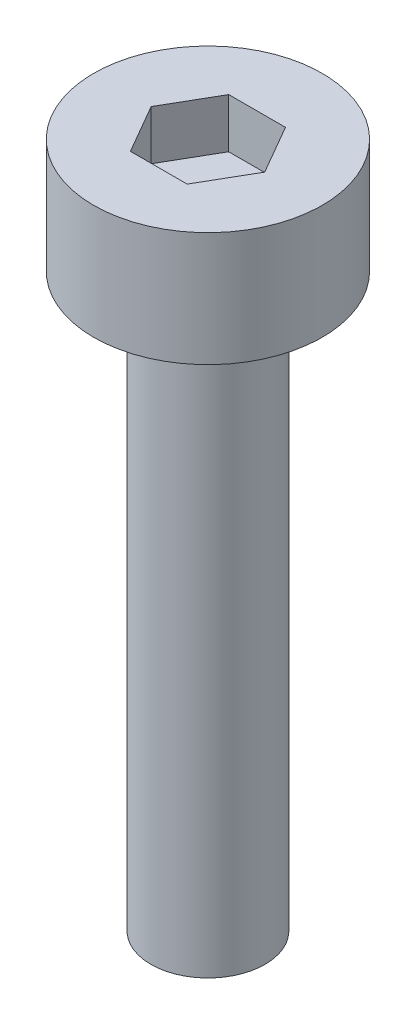
SolidWorks part; units mm, degrees
ref_plane "Front Plane" through (0, 0, 0) normal (0, 0, 1) x (1, 0, 0)
ref_plane "Top Plane" through (0, 0, 0) normal (0, 1, 0) x (1, 0, 0)
ref_plane "Right Plane" through (0, 0, 0) normal (1, 0, 0) x (0, 0, -1)
sketch "Sketch1" plane through (0, 0, 0) normal (0, 1, 0) x (1, 0, 0)
  circle A0 centre (0, 0) radius 1.5
  dimension "D1" = 3
extrude "ScrewShaft" add sketch "Sketch1" along normal blind 15
sketch "Sketch2" plane through (0, 15, 0) normal (0, 1, 0) x (1, 0, 0)
  circle A0 centre (0, 0) radius 3
  dimension "D1" = 6
extrude "Boss-Extrude2" add sketch "Sketch2" along normal blind 3
sketch "Sketch3" plane through (0, 18, 0) normal (0, 1, 0) x (1, 0, 0)
  line L0 (0, 0) -> (0, 1.29) construction
  line L1 (1.4896, 0) -> (0.7448, 1.29)
  line L2 (0.7448, 1.29) -> (-0.7448, 1.29)
  line L3 (-0.7448, 1.29) -> (-1.4896, 0)
  line L4 (-1.4896, 0) -> (-0.7448, -1.29)
  line L5 (-0.7448, -1.29) -> (0.7448, -1.29)
  line L6 (0.7448, -1.29) -> (1.4896, 0)
  circle A0 centre (0, 0) radius 1.29 construction
  dimension "D1" = 2.58
extrude "Cut-Extrude1" cut sketch "Sketch3" against normal blind 1.3
equation "\"X-ROD-SPACING\"=45"
equation "\"Y-ROD-SPACING\"=75"
equation "\"Z-ROD-SPACING\"=17.5"
equation "\"Y-BED-OFFSET\"=2"
equation "\"Y-BED-ROD-INSET\"=3.5"
equation "\"T-SLOT-NUT-FILLET-RADIUS\"=0.5"
equation "\"T-SLOT-SCREW-SHAFT-RADIUS\"=1.55"
equation "\"T-SLOT-SCREW-SHAFT-CUTOUT-LENGTH\"=11.0"
equation "\"T-SLOT-NUT-DEPTH\"=3.5"
equation "\"T-SLOT-NUT-WIDTH\"=2.85"
equation "\"T-SLOT-NUT-END-DISTANCE\"=8"
equation "\"ACRYLIC-THICKNESS\"=10"
equation "\"ACRYLIC-THICKNESS2\"=4.5"
equation "\"ACRYLIC-TAB-CUTOUT-SIZE\"=\"ACRYLIC-THICKNESS\"+\"ACRYLIC-TAB-TOLERANCE\"*2"
equation "\"ACRYLIC-TAB-WIDTH\"=\"ACRYLIC-THICKNESS\""
equation "\"ACRYLIC-M3-HOLE\"=2.9"
equation "\"SMOOTHROD-CAP-SCREW-DISTANCE\"=20"
equation "\"FRAME-WIDTH-INNER\"=370"
equation "\"NEMA17-HOLE-SPACING\"=31"
equation "\"NEMA17-CENTRAL-CUTOUT\"=22.5"
equation "\"Z-BRACKET-REACH\"=55"
equation "\"TOP-BRACKET-SPACING\"=40"
equation "\"SMOOTHROD-X-LENGTH\"=350"
equation "\"SMOOTHROD-Y-LENGTH\"=350"
equation "\"SMOOTHROD-Z-LENGTH\"=350"
equation "\"SMOOTHROD-TIGHTENING-HEADROOM\"=.25"
equation "\"LEADSCREW-Z-LENGTH\"=300"
equation "\"SCREW-LENGTH-FRAME\"=\"ACRYLIC-THICKNESS\" + 10"
equation "\"SCREW-HEAD-RADIUS\"=6"
equation "\"PRINTED-X-SMOOTHROD-DIAMETER\"=9.0"
equation "\"PRINTED-X-SMOOTHROD-CUTOUT\"=10"
equation "\"PRINTED-X-BASE-HEIGHT\"=10"
equation "\"PRINTED-LM8UU-CUTOUT-SIZE\"=15.5"
equation "\"PRINTED-LM8UU-CUTOUT-LENGTH\"=24.5"
equation "\"PRINTED-X-IDLER-HEIGHT\"=16"
equation "\"PSU-MOUNTING-WIDTH\"=95"
equation "\"PSU-MOUNTING-HEIGHT\"=177"
equation "\"D1@ScrewShaft\"=\"SCREW-LENGTH-MOTOR\""
equation "\"D1@Sketch2\"=\"SCREW-HEAD-RADIUS\""
equation "\"Y-BED-SCREW-SPACING\"=209"
equation "\"Y-BED-SCREW-CUTOUT-SLOT-HEIGHT\"=2"
equation "\"Z-ROD-INSET\"=16"
equation "\"SCREW-LENGTH-MOTOR\"=\"ACRYLIC-THICKNESS\" + 5"
equation "\"Y-BELT-TO-ROD-DISTANCE\"=20"
equation "\"SPOOL-HOLDER-ROD-SPACING\"=150"
